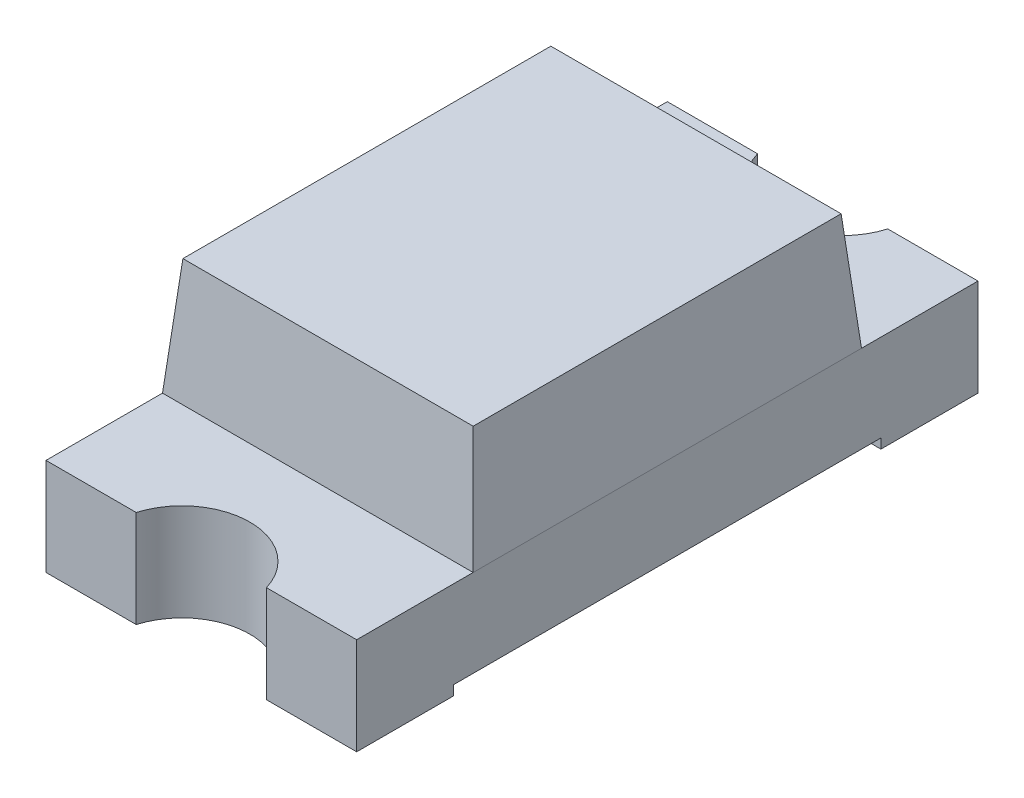
SolidWorks part; units mm, degrees
ref_plane "Front Plane" through (0, 0, 0) normal (0, 0, 1) x (1, 0, 0)
ref_plane "Top Plane" through (0, 0, 0) normal (0, 1, 0) x (1, 0, 0)
ref_plane "Right Plane" through (0, 0, 0) normal (1, 0, 0) x (0, 0, -1)
sketch "Sketch1" plane through (0, 0, 0) normal (1, 0, 0) x (0, 0, -1)
  line L0 (1.1, 0) -> (1.6, 0)
  line L1 (-1.6, 0.5) -> (1.6, 0.5)
  line L2 (-1.6, 0.5) -> (-1.6, 0)
  line L3 (-1.6, 0) -> (-1.1, 0)
  line L4 (1.6, 0.5) -> (1.6, 0)
  line L5 (-1.1, 0.05) -> (1.1, 0.05)
  line L6 (-1.1, 0.05) -> (-1.1, 0)
  line L8 (1.1, 0.05) -> (1.1, 0)
  dimension "D1" = 3.2
  dimension "D2" = 0.5
  dimension "D3" = 0.05
  dimension "D4" = 2.2
  dimension "D5" = 1.1
extrude "Extrude1" add sketch "Sketch1" along normal blind 0.8 and the other way blind 0.8
sketch "Sketch2" plane through (0, 0, 0) normal (0, 1, 0) x (1, 0, 0)
  circle A0 centre (0, 1.7) radius 0.35
  circle A1 centre (0, -1.7) radius 0.35
extrude "Cut-Extrude1" cut sketch "Sketch2" along normal through all
sketch "Sketch3" plane through (0, 0.5, 0) normal (0, 1, 0) x (-1, 0, 0)
  line L1 (0.4574, -1) -> (0.2774, -1)
  line L2 (0.4574, -1) -> (0.4574, -0.4507)
  line L3 (0.225, -0.225) -> (-0.225, -0.225)
  line L4 (0.2774, -1) -> (0.2774, -0.6307)
  line L5 (0.4574, -0.4507) -> (-0.2764, -0.4507)
  line L7 (0.2774, -0.6307) -> (-0.2764, -0.6307)
  line L8 (-0.2764, -0.4507) -> (-0.2764, -0.6307)
  line L9 (0.225, -0.225) -> (0.225, 0.4637)
  line L10 (0.075, 0.225) -> (-0.225, 0.225)
  line L11 (-0.225, -0.225) -> (-0.225, 0.225)
  line L13 (0.225, 0.4637) -> (0.225, 0.7354)
  line L15 (0.075, 0.225) -> (0.075, 0.525)
  line L16 (0.075, 0.525) -> (-0.2794, 0.525)
  line L17 (0.225, 0.7354) -> (0.225, 0.675)
  line L18 (0.225, 0.675) -> (-0.3274, 0.675)
  line L20 (-0.2794, 0.525) -> (-0.4774, 0.525)
  line L21 (-0.3274, 0.675) -> (-0.3274, 1)
  line L22 (-0.3274, 1) -> (-0.4774, 1)
  line L23 (-0.4774, 0.525) -> (-0.4774, 1)
  dimension "D1" = 0.45
  dimension "D2" = 0.45
  dimension "D3" = 0.225
  dimension "D4" = 0.225
  dimension "D5" = 0.15
  dimension "D6" = 0.15
  dimension "D7" = 0.15
  dimension "D8" = 0.3
  dimension "D9" = 1
  dimension "D10" = 1
  dimension "D11" = 0.18
  dimension "D12" = 0.18
extrude "Cut-Extrude2" cut sketch "Sketch3" against normal blind 0.005 contours L23 L20 L16 L15 L10 L11 L3 L9 L13 L18 L21 L22 | L5 L8 L7 L4 L1 L2 region at (-0.3674, 0.5, -0.9908) region at (0, 0.5, -0.2109)
sketch "Sketch4" plane through (0, 0.495, 0) normal (0, 1, 0) x (-1, 0, 0)
  line L1 (0.195, -0.195) -> (-0.195, -0.195)
  line L2 (0.195, -0.195) -> (0.195, 0.195)
  line L3 (0.195, 0.195) -> (-0.195, 0.195)
  line L4 (-0.195, -0.195) -> (-0.195, 0.195)
  dimension "D1" = 0.39
  dimension "D2" = 0.39
  dimension "D3" = 0.195
  dimension "D4" = 0.195
extrude "Extrude2" add sketch "Sketch4" along normal blind 0.25
sketch "Sketch5" plane through (0, 0.5, 0) normal (0, 1, 0) x (-1, 0, 0)
  line L0 (0.8, -1.6) -> (0.8, 1.6) construction
  line L1 (0.8, -1) -> (-0.8, -1)
  line L2 (0.8, -1) -> (0.8, 1)
  line L3 (0.8, 1) -> (-0.8, 1)
  line L4 (-0.8, -1) -> (-0.8, 1)
  line L5 (-0.8, -1.6) -> (-0.8, 1.6) construction
  dimension "D1" = 2
extrude "Extrude3" add sketch "Sketch5" along normal blind 0.6 draft 5 separate body
